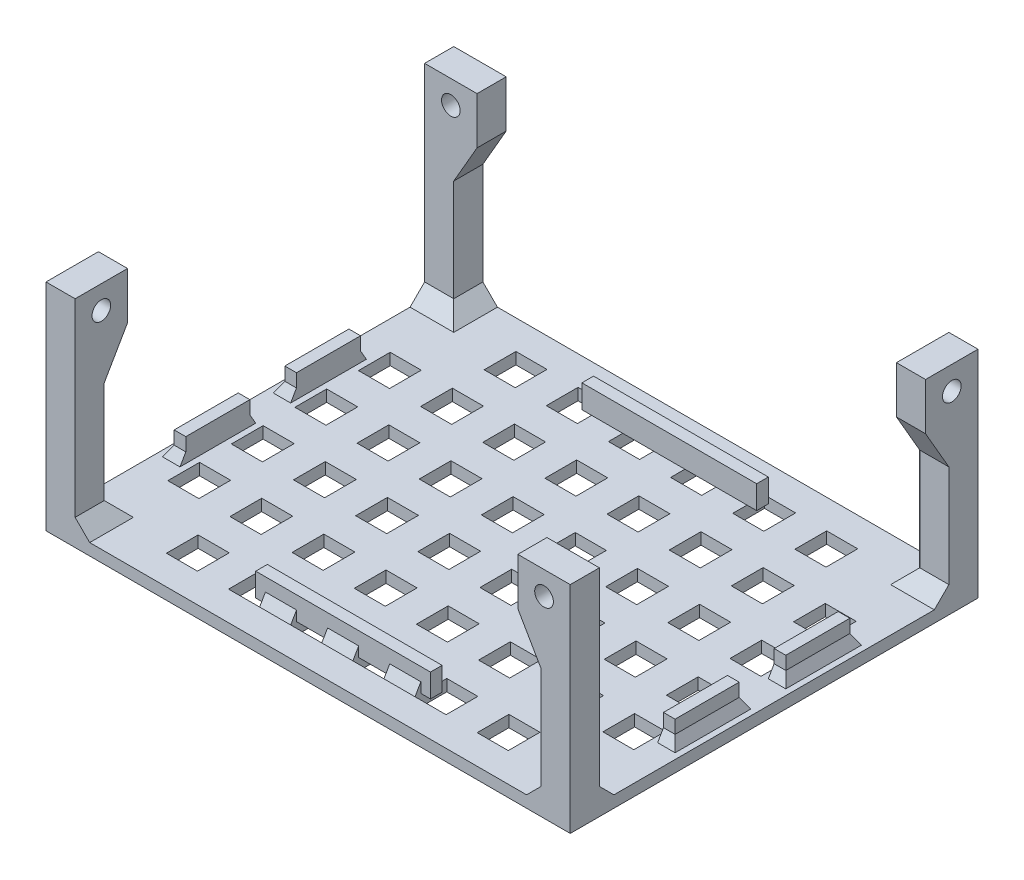
SolidWorks part; units mm, degrees
ref_plane "Plano frontal" through (0, 0, 0) normal (0, 0, 1) x (1, 0, 0)
ref_plane "Plano superior" through (0, 0, 0) normal (0, 1, 0) x (1, 0, 0)
ref_plane "Plano direito" through (0, 0, 0) normal (1, 0, 0) x (0, 0, -1)
sketch "Esboço1" plane through (0, 0, 0) normal (0, 1, 0) x (1, 0, 0)
  line L1 (-45, -35) -> (45, -35)
  line L2 (-45, -35) -> (-45, 35)
  line L3 (-45, 35) -> (45, 35)
  line L4 (45, -35) -> (45, 35)
  line L5 (-45, -35) -> (45, 35) construction
  line L6 (-45, 35) -> (45, -35) construction
  point P0 (0, 0)
  dimension "D1" = 90
  dimension "D2" = 70
extrude "Ressalto-extrusão1" add sketch "Esboço1" along normal blind 2
sketch "Esboço2" plane through (0, 2, 0) normal (0, 1, 0) x (1, 0, 0)
  line L0 (-29.33, 30) -> (-29.33, 24.55)
  line L7 (-40, 30) -> (-34.666, 30)
  line L10 (-45, 35) -> (-45, -35) construction
  line L11 (-40, -30) -> (40, -30)
  line L12 (-40, -30) -> (-40, 30)
  line L13 (-40, 30) -> (40, 30)
  line L14 (40, -30) -> (40, 30)
  line L15 (-40, -30) -> (40, 30) construction
  line L16 (-40, 30) -> (40, -30) construction
  line L17 (45, 35) -> (-45, 35) construction
  line L18 (-40, 30) -> (-40, 24.55)
  line L19 (-40, 24.55) -> (-34.666, 24.55)
  line L20 (-34.666, 30) -> (-34.666, 24.55)
  line L21 (-23.996, 30) -> (-23.996, 24.55)
  line L22 (-29.33, 30) -> (-23.996, 30)
  line L23 (-29.33, 24.55) -> (-23.996, 24.55)
  line L24 (-18.66, 30) -> (-18.66, 24.55)
  line L25 (-13.326, 30) -> (-13.326, 24.55)
  line L26 (-18.66, 30) -> (-13.326, 30)
  line L27 (-18.66, 24.55) -> (-13.326, 24.55)
  line L28 (-7.99, 30) -> (-7.99, 24.55)
  line L29 (-2.656, 30) -> (-2.656, 24.55)
  line L30 (-7.99, 30) -> (-2.656, 30)
  line L31 (-7.99, 24.55) -> (-2.656, 24.55)
  line L32 (2.68, 30) -> (2.68, 24.55)
  line L33 (8.014, 30) -> (8.014, 24.55)
  line L34 (2.68, 30) -> (8.014, 30)
  line L35 (2.68, 24.55) -> (8.014, 24.55)
  line L36 (13.35, 30) -> (13.35, 24.55)
  line L37 (18.684, 30) -> (18.684, 24.55)
  line L38 (13.35, 30) -> (18.684, 30)
  line L39 (13.35, 24.55) -> (18.684, 24.55)
  line L40 (24.02, 30) -> (24.02, 24.55)
  line L41 (29.354, 30) -> (29.354, 24.55)
  line L42 (24.02, 30) -> (29.354, 30)
  line L43 (24.02, 24.55) -> (29.354, 24.55)
  line L44 (34.69, 30) -> (34.69, 24.55)
  line L45 (40.024, 30) -> (40.024, 24.55)
  line L46 (34.69, 30) -> (40.024, 30)
  line L47 (34.69, 24.55) -> (40.024, 24.55)
  line L48 (-29.33, 19.09) -> (-29.33, 13.64)
  line L49 (-23.996, 19.09) -> (-23.996, 13.64)
  line L50 (-29.33, 19.09) -> (-23.996, 19.09)
  line L51 (-29.33, 13.64) -> (-23.996, 13.64)
  line L52 (-18.66, 19.09) -> (-18.66, 13.64)
  line L53 (-13.326, 19.09) -> (-13.326, 13.64)
  line L54 (-18.66, 19.09) -> (-13.326, 19.09)
  line L55 (-18.66, 13.64) -> (-13.326, 13.64)
  line L56 (-7.99, 19.09) -> (-7.99, 13.64)
  line L57 (-2.656, 19.09) -> (-2.656, 13.64)
  line L58 (-7.99, 19.09) -> (-2.656, 19.09)
  line L59 (-7.99, 13.64) -> (-2.656, 13.64)
  line L60 (2.68, 19.09) -> (2.68, 13.64)
  line L61 (8.014, 19.09) -> (8.014, 13.64)
  line L62 (2.68, 19.09) -> (8.014, 19.09)
  line L63 (2.68, 13.64) -> (8.014, 13.64)
  line L64 (13.35, 19.09) -> (13.35, 13.64)
  line L65 (18.684, 19.09) -> (18.684, 13.64)
  line L66 (13.35, 19.09) -> (18.684, 19.09)
  line L67 (13.35, 13.64) -> (18.684, 13.64)
  line L68 (24.02, 19.09) -> (24.02, 13.64)
  line L69 (29.354, 19.09) -> (29.354, 13.64)
  line L70 (24.02, 19.09) -> (29.354, 19.09)
  line L71 (24.02, 13.64) -> (29.354, 13.64)
  line L72 (34.69, 19.09) -> (34.69, 13.64)
  line L73 (40.024, 19.09) -> (40.024, 13.64)
  line L74 (34.69, 19.09) -> (40.024, 19.09)
  line L75 (34.69, 13.64) -> (40.024, 13.64)
  line L76 (-29.33, 8.18) -> (-29.33, 2.73)
  line L77 (-23.996, 8.18) -> (-23.996, 2.73)
  line L78 (-29.33, 8.18) -> (-23.996, 8.18)
  line L79 (-29.33, 2.73) -> (-23.996, 2.73)
  line L80 (-18.66, 8.18) -> (-18.66, 2.73)
  line L81 (-13.326, 8.18) -> (-13.326, 2.73)
  line L82 (-18.66, 8.18) -> (-13.326, 8.18)
  line L83 (-18.66, 2.73) -> (-13.326, 2.73)
  line L84 (-7.99, 8.18) -> (-7.99, 2.73)
  line L85 (-2.656, 8.18) -> (-2.656, 2.73)
  line L86 (-7.99, 8.18) -> (-2.656, 8.18)
  line L87 (-7.99, 2.73) -> (-2.656, 2.73)
  line L88 (2.68, 8.18) -> (2.68, 2.73)
  line L89 (8.014, 8.18) -> (8.014, 2.73)
  line L90 (2.68, 8.18) -> (8.014, 8.18)
  line L91 (2.68, 2.73) -> (8.014, 2.73)
  line L92 (13.35, 8.18) -> (13.35, 2.73)
  line L93 (18.684, 8.18) -> (18.684, 2.73)
  line L94 (13.35, 8.18) -> (18.684, 8.18)
  line L95 (13.35, 2.73) -> (18.684, 2.73)
  line L96 (24.02, 8.18) -> (24.02, 2.73)
  line L97 (29.354, 8.18) -> (29.354, 2.73)
  line L98 (24.02, 8.18) -> (29.354, 8.18)
  line L99 (24.02, 2.73) -> (29.354, 2.73)
  line L100 (34.69, 8.18) -> (34.69, 2.73)
  line L101 (40.024, 8.18) -> (40.024, 2.73)
  line L102 (34.69, 8.18) -> (40.024, 8.18)
  line L103 (34.69, 2.73) -> (40.024, 2.73)
  line L104 (-29.33, -2.73) -> (-29.33, -8.18)
  line L105 (-23.996, -2.73) -> (-23.996, -8.18)
  line L106 (-29.33, -2.73) -> (-23.996, -2.73)
  line L107 (-29.33, -8.18) -> (-23.996, -8.18)
  line L108 (-18.66, -2.73) -> (-18.66, -8.18)
  line L109 (-13.326, -2.73) -> (-13.326, -8.18)
  line L110 (-18.66, -2.73) -> (-13.326, -2.73)
  line L111 (-18.66, -8.18) -> (-13.326, -8.18)
  line L112 (-7.99, -2.73) -> (-7.99, -8.18)
  line L113 (-2.656, -2.73) -> (-2.656, -8.18)
  line L114 (-7.99, -2.73) -> (-2.656, -2.73)
  line L115 (-7.99, -8.18) -> (-2.656, -8.18)
  line L116 (2.68, -2.73) -> (2.68, -8.18)
  line L117 (8.014, -2.73) -> (8.014, -8.18)
  line L118 (2.68, -2.73) -> (8.014, -2.73)
  line L119 (2.68, -8.18) -> (8.014, -8.18)
  line L120 (13.35, -2.73) -> (13.35, -8.18)
  line L121 (18.684, -2.73) -> (18.684, -8.18)
  line L122 (13.35, -2.73) -> (18.684, -2.73)
  line L123 (13.35, -8.18) -> (18.684, -8.18)
  line L124 (24.02, -2.73) -> (24.02, -8.18)
  line L125 (29.354, -2.73) -> (29.354, -8.18)
  line L126 (24.02, -2.73) -> (29.354, -2.73)
  line L127 (24.02, -8.18) -> (29.354, -8.18)
  line L128 (34.69, -2.73) -> (34.69, -8.18)
  line L129 (40.024, -2.73) -> (40.024, -8.18)
  line L130 (34.69, -2.73) -> (40.024, -2.73)
  line L131 (34.69, -8.18) -> (40.024, -8.18)
  line L132 (-29.33, -13.64) -> (-29.33, -19.09)
  line L133 (-23.996, -13.64) -> (-23.996, -19.09)
  line L134 (-29.33, -13.64) -> (-23.996, -13.64)
  line L135 (-29.33, -19.09) -> (-23.996, -19.09)
  line L136 (-18.66, -13.64) -> (-18.66, -19.09)
  line L137 (-13.326, -13.64) -> (-13.326, -19.09)
  line L138 (-18.66, -13.64) -> (-13.326, -13.64)
  line L139 (-18.66, -19.09) -> (-13.326, -19.09)
  line L140 (-7.99, -13.64) -> (-7.99, -19.09)
  line L141 (-2.656, -13.64) -> (-2.656, -19.09)
  line L142 (-7.99, -13.64) -> (-2.656, -13.64)
  line L143 (-7.99, -19.09) -> (-2.656, -19.09)
  line L144 (2.68, -13.64) -> (2.68, -19.09)
  line L145 (8.014, -13.64) -> (8.014, -19.09)
  line L146 (2.68, -13.64) -> (8.014, -13.64)
  line L147 (2.68, -19.09) -> (8.014, -19.09)
  line L148 (13.35, -13.64) -> (13.35, -19.09)
  line L149 (18.684, -13.64) -> (18.684, -19.09)
  line L150 (13.35, -13.64) -> (18.684, -13.64)
  line L151 (13.35, -19.09) -> (18.684, -19.09)
  line L152 (24.02, -13.64) -> (24.02, -19.09)
  line L153 (29.354, -13.64) -> (29.354, -19.09)
  line L154 (24.02, -13.64) -> (29.354, -13.64)
  line L155 (24.02, -19.09) -> (29.354, -19.09)
  line L156 (34.69, -13.64) -> (34.69, -19.09)
  line L157 (40.024, -13.64) -> (40.024, -19.09)
  line L158 (34.69, -13.64) -> (40.024, -13.64)
  line L159 (34.69, -19.09) -> (40.024, -19.09)
  line L160 (-29.33, -24.55) -> (-29.33, -30)
  line L161 (-23.996, -24.55) -> (-23.996, -30)
  line L162 (-29.33, -24.55) -> (-23.996, -24.55)
  line L163 (-29.33, -30) -> (-23.996, -30)
  line L164 (-18.66, -24.55) -> (-18.66, -30)
  line L165 (-13.326, -24.55) -> (-13.326, -30)
  line L166 (-18.66, -24.55) -> (-13.326, -24.55)
  line L167 (-18.66, -30) -> (-13.326, -30)
  line L168 (-7.99, -24.55) -> (-7.99, -30)
  line L169 (-2.656, -24.55) -> (-2.656, -30)
  line L170 (-7.99, -24.55) -> (-2.656, -24.55)
  line L171 (-7.99, -30) -> (-2.656, -30)
  line L172 (2.68, -24.55) -> (2.68, -30)
  line L173 (8.014, -24.55) -> (8.014, -30)
  line L174 (2.68, -24.55) -> (8.014, -24.55)
  line L175 (2.68, -30) -> (8.014, -30)
  line L176 (13.35, -24.55) -> (13.35, -30)
  line L177 (18.684, -24.55) -> (18.684, -30)
  line L178 (13.35, -24.55) -> (18.684, -24.55)
  line L179 (13.35, -30) -> (18.684, -30)
  line L180 (24.02, -24.55) -> (24.02, -30)
  line L181 (29.354, -24.55) -> (29.354, -30)
  line L182 (24.02, -24.55) -> (29.354, -24.55)
  line L183 (24.02, -30) -> (29.354, -30)
  line L184 (34.69, -24.55) -> (34.69, -30)
  line L185 (40.024, -24.55) -> (40.024, -30)
  line L186 (34.69, -24.55) -> (40.024, -24.55)
  line L187 (34.69, -30) -> (40.024, -30)
  line L188 (-40, 19.09) -> (-40, 13.64)
  line L189 (-34.666, 19.09) -> (-34.666, 13.64)
  line L190 (-40, 19.09) -> (-34.666, 19.09)
  line L191 (-40, 13.64) -> (-34.666, 13.64)
  line L192 (-40, 8.18) -> (-40, 2.73)
  line L193 (-34.666, 8.18) -> (-34.666, 2.73)
  line L194 (-40, 8.18) -> (-34.666, 8.18)
  line L195 (-40, 2.73) -> (-34.666, 2.73)
  line L196 (-40, -2.73) -> (-40, -8.18)
  line L197 (-34.666, -2.73) -> (-34.666, -8.18)
  line L198 (-40, -2.73) -> (-34.666, -2.73)
  line L199 (-40, -8.18) -> (-34.666, -8.18)
  line L200 (-40, -13.64) -> (-40, -19.09)
  line L201 (-34.666, -13.64) -> (-34.666, -19.09)
  line L202 (-40, -13.64) -> (-34.666, -13.64)
  line L203 (-40, -19.09) -> (-34.666, -19.09)
  line L204 (-40, -24.55) -> (-40, -30)
  line L205 (-34.666, -24.55) -> (-34.666, -30)
  line L206 (-40, -24.55) -> (-34.666, -24.55)
  line L207 (-40, -30) -> (-34.666, -30)
  point P0 (0, 0)
  dimension "D1" = 5
  dimension "D2" = 5
  dimension "D3" = 5.334
  dimension "D4" = 5.45
  dimension "D5" = 6
sketch "Esboço3" plane through (0, 2, 0) normal (0, 1, 0) x (1, 0, 0)
  line L0 (40, 35) -> (45, 35)
  line L5 (-45, 35) -> (-40, 35)
  line L6 (-45, 35) -> (-45, 30)
  line L7 (-45, 30) -> (-40, 30)
  line L8 (-40, 35) -> (-40, 30)
  line L9 (45, 35) -> (45, 30)
  line L10 (40, 30) -> (45, 30)
  line L11 (40, 35) -> (40, 30)
  line L12 (40, -30) -> (45, -30)
  line L13 (45, -30) -> (45, -35)
  line L14 (40, -35) -> (45, -35)
  line L15 (40, -30) -> (40, -35)
  line L16 (-45, -30) -> (-40, -30)
  line L17 (-40, -30) -> (-40, -35)
  line L18 (-45, -35) -> (-40, -35)
  line L19 (-45, -30) -> (-45, -35)
  dimension "D1" = 5
  dimension "D2" = 5
  dimension "D3" = 2
extrude "Ressalto-extrusão2" add sketch "Esboço3" along normal blind 35
sketch "Esboço4" plane through (0, 2, 0) normal (0, 1, 0) x (1, 0, 0)
  line L0 (0, 35) -> (0, -35) construction
  line L1 (40, 35) -> (-40, 35) construction
  line L2 (-40, -35) -> (40, -35) construction
  line L3 (-45, 0) -> (45, 0) construction
  line L4 (-15, 27) -> (15, 27)
  line L5 (-15, 27) -> (-15, 29)
  line L6 (-15, 29) -> (15, 29)
  line L7 (15, 27) -> (15, 29)
  line L8 (-15, 27) -> (15, 29) construction
  line L9 (-15, 29) -> (15, 27) construction
  line L10 (-15, -27) -> (15, -27)
  line L11 (-15, -27) -> (-15, -29)
  line L12 (-15, -29) -> (15, -29)
  line L13 (15, -27) -> (15, -29)
  line L14 (-15, -27) -> (15, -29) construction
  line L15 (-15, -29) -> (15, -27) construction
  line L16 (-45, 30) -> (-45, -30) construction
  line L17 (45, -30) -> (45, 30) construction
  line L18 (43, 4) -> (43, 15)
  line L25 (41, -15) -> (43, -15)
  line L26 (41, -15) -> (41, -4)
  line L27 (41, 15) -> (43, 15)
  line L28 (43, -15) -> (43, -4)
  line L29 (41, -15) -> (43, 15) construction
  line L30 (41, 15) -> (43, -15) construction
  line L37 (41, -4) -> (43, -4)
  line L39 (41, 4) -> (43, 4)
  line L41 (41, -4) -> (43, 4) construction
  line L42 (41, 4) -> (43, -4) construction
  line L43 (41, 4) -> (41, 15)
  line L50 (-41, 4) -> (-41, 15)
  line L51 (-43, -15) -> (-41, -15)
  line L52 (-43, -15) -> (-43, -4)
  line L53 (-43, 15) -> (-41, 15)
  line L54 (-41, -15) -> (-41, -4)
  line L55 (-43, -4) -> (-41, -4)
  line L56 (-43, 4) -> (-41, 4)
  line L57 (-43, 4) -> (-43, 15)
  line L58 (-43, -15) -> (-41, 15) construction
  line L59 (-43, 15) -> (-41, -15) construction
  line L60 (-43, -4) -> (-41, 4) construction
  line L61 (-43, 4) -> (-41, -4) construction
  point P6 (0, 28)
  point P11 (0, -28)
  point P17 (-42, 0)
  point P28 (-42, 0)
  point P30 (42, 0)
  point P40 (42, 0)
  dimension "D2" = 2
  dimension "D3" = 2
  dimension "D4" = 30
  dimension "D5" = 30
  dimension "D6" = 27
  dimension "D10" = 2
  dimension "D11" = 54
  dimension "D12" = 30
  dimension "D14" = 8
extrude "Ressalto-extrusão4" add sketch "Esboço4" along normal blind 4
extrude "Corte-extrusão2" cut sketch "Esboço2" against normal through all contours L0 L23 L21 L13 | L12 L191 L189 L190 | L48 L51 L49 L50 | L12 L195 L193 L194 | L76 L79 L77 L78 | L12 L199 L197 L198 | L104 L107 L105 L106 | L12 L203 L201 L202 | L132 L135 L133 L134 | L136 L139 L137 L138 | L108 L111 L109 L110 | L80 L83 L81 L82 | L52 L55 L53 L54 | L24 L27 L25 L13 | L28 L31 L29 L13 | L56 L59 L57 L58 | L84 L87 L85 L86 | L112 L115 L113 L114 | L140 L143 L141 L142 | L144 L147 L145 L146 | L116 L119 L117 L118 | L88 L91 L89 L90 | L60 L63 L61 L62 | L32 L35 L33 L13 | L36 L39 L37 L13 | L64 L67 L65 L66 | L92 L95 L93 L94 | L120 L123 L121 L122 | L148 L151 L149 L150 | L152 L155 L153 L154 | L124 L127 L125 L126 | L96 L99 L97 L98 | L68 L71 L69 L70 | L40 L43 L41 L13 | L72 L75 L14 L74 | L100 L103 L14 L102 | L128 L131 L14 L130 | L156 L159 L14 L158 | L162 L160 L11 L161 | L166 L164 L11 L165 | L170 L168 L11 L169 | L174 L172 L11 L173 | L178 L176 L11 L177 | L182 L180 L11 L181 region at (-26.663, 2, -27.275) region at (-15.993, 2, -27.275) region at (-37.333, 2, -16.365) region at (-5.323, 2, -27.275) region at (-37.333, 2, -5.455) region at (5.347, 2, -27.275) region at (-37.333, 2, 5.455) region at (16.017, 2, -27.275) region at (-37.333, 2, 16.365) region at (26.687, 2, -27.275) region at (-26.663, 2, 27.275) region at (37.345, 2, -16.365) region at (-15.993, 2, 27.275) region at (37.345, 2, -5.455) region at (-5.323, 2, 27.275) region at (37.345, 2, 5.455) region at (5.347, 2, 27.275) region at (37.345, 2, 16.365) region at (16.017, 2, 27.275) region at (26.687, 2, 27.275) region at (-26.663, 2, -16.365) region at (-15.993, 2, -16.365) region at (-5.323, 2, -16.365) region at (5.347, 2, -16.365) region at (16.017, 2, -16.365) region at (26.687, 2, -16.365) region at (-26.663, 2, -5.455) region at (-15.993, 2, -5.455) region at (-5.323, 2, -5.455) region at (5.347, 2, -5.455) region at (16.017, 2, -5.455) region at (26.687, 2, -5.455) region at (-26.663, 2, 5.455) region at (-15.993, 2, 5.455) region at (-5.323, 2, 5.455) region at (5.347, 2, 5.455) region at (16.017, 2, 5.455) region at (26.687, 2, 5.455) region at (-26.663, 2, 16.365) region at (-15.993, 2, 16.365) region at (-5.323, 2, 16.365) region at (5.347, 2, 16.365) region at (16.017, 2, 16.365) region at (26.687, 2, 16.365)
chamfer "Chanfro2" distance 2.5 angle 45 8 edges at (-40, 2, 32.5) (-42.5, 2, 30) (42.5, 2, 30) (40, 2, 32.5) (40, 2, -32.5) (42.5, 2, -30) (-40, 2, -32.5) (-42.5, 2, -30)
chamfer "Chanfro3" distance 1 angle 60 18 edges at (-10.658, 2, -29) (0.012, 2, -29) (10.682, 2, -29) (-42, 2, -15) (-43, 2, -9.5) (-42, 2, -4) (-42, 2, 4) (-43, 2, 9.5) (-42, 2, 15) (42, 2, -15) (42, 2, -4) (43, 2, -9.5) (42, 2, 4) (42, 2, 15) (43, 2, 9.5) (10.682, 2, 29) (-10.658, 2, 29) (0.012, 2, 29) first distance on face at (-5.323, 2, 5.455)
sketch "Esboço6" plane through (0, 0, 30) normal (0, 0, -1) x (-1, 0, 0)
  line L0 (45, 37) -> (45, 4.5) construction
  line L1 (40, 37) -> (45, 37)
  line L2 (40, 37) -> (40, 29)
  line L3 (40, 29) -> (45, 29)
  line L4 (45, 37) -> (45, 29)
  dimension "D1" = 8
extrude "Ressalto-extrusão6" add sketch "Esboço6" along normal blind 4
sketch "Esboço7" plane through (40, 0, 0) normal (-1, 0, 0) x (0, 0, 1)
  line L0 (35, 37) -> (35, 4.5) construction
  line L1 (30, 37) -> (35, 37)
  line L2 (30, 37) -> (30, 29)
  line L3 (30, 29) -> (35, 29)
  line L4 (35, 37) -> (35, 29)
  dimension "D1" = 8
extrude "Ressalto-extrusão7" add sketch "Esboço7" along normal blind 4
sketch "Esboço8" plane through (-40, 0, 0) normal (1, 0, 0) x (0, 0, -1)
  line L0 (35, 37) -> (35, 4.5) construction
  line L1 (30, 37) -> (35, 37)
  line L2 (30, 37) -> (30, 29)
  line L3 (30, 29) -> (35, 29)
  line L4 (35, 37) -> (35, 29)
  dimension "D1" = 8
extrude "Ressalto-extrusão8" add sketch "Esboço8" along normal blind 4
sketch "Esboço9" plane through (0, 0, -30) normal (0, 0, 1) x (1, 0, 0)
  line L0 (45, 37) -> (45, 4.5) construction
  line L1 (40, 37) -> (45, 37)
  line L2 (40, 37) -> (40, 29)
  line L3 (40, 29) -> (45, 29)
  line L4 (45, 37) -> (45, 29)
  dimension "D1" = 8
extrude "Ressalto-extrusão9" add sketch "Esboço9" along normal blind 4
chamfer "Chanfro4" distance 7 angle 30 4 edges at (-42.5, 29, 30) (40, 29, 32.5) (42.5, 29, -30) (-40, 29, -32.5) first distance on face at (-42.5, 16.75, 30) first distance on face at (40, 16.75, 32.5) first distance on face at (42.5, 16.75, -30) first distance on face at (-40, 16.75, -32.5)
sketch "Esboço10" plane through (-45, 0, 0) normal (-1, 0, 0) x (0, 0, 1)
  line L0 (26, 37) -> (35, 37) construction
  line L1 (30.5, 37) -> (30.5, 21.931) construction
  circle A0 centre (30.5, 33) radius 1.6
  dimension "D1" = 3.2
  dimension "D2" = 4
extrude "Corte-extrusão3" cut sketch "Esboço10" against normal blind 5
sketch "Esboço11" plane through (0, 0, -35) normal (0, 0, -1) x (-1, 0, 0)
  line L0 (40.5, 37) -> (40.5, 30.0036) construction
  line L1 (36, 37) -> (45, 37) construction
  line L2 (36, 28.9282) -> (36, 37) construction
  line L3 (45, 37) -> (45, 0) construction
  circle A0 centre (40.5, 33) radius 1.6
  dimension "D2" = 3.2
  dimension "D1" = 4
extrude "Corte-extrusão4" cut sketch "Esboço11" against normal blind 5
sketch "Esboço12" plane through (45, 0, 0) normal (1, 0, 0) x (0, 0, -1)
  line L0 (30.5, 37) -> (30.5, 27.9486) construction
  line L1 (26, 37) -> (35, 37) construction
  circle A0 centre (30.5, 33) radius 1.6
  dimension "D2" = 3.2
  dimension "D1" = 4
extrude "Corte-extrusão5" cut sketch "Esboço12" against normal blind 5
sketch "Esboço13" plane through (0, 0, 35) normal (0, 0, 1) x (1, 0, 0)
  line L0 (40.5, 37) -> (40.5, 27.8714) construction
  line L1 (36, 37) -> (45, 37) construction
  circle A0 centre (40.5, 33) radius 1.6
  dimension "D2" = 3.2
  dimension "D1" = 4
extrude "Corte-extrusão6" cut sketch "Esboço13" against normal blind 5
